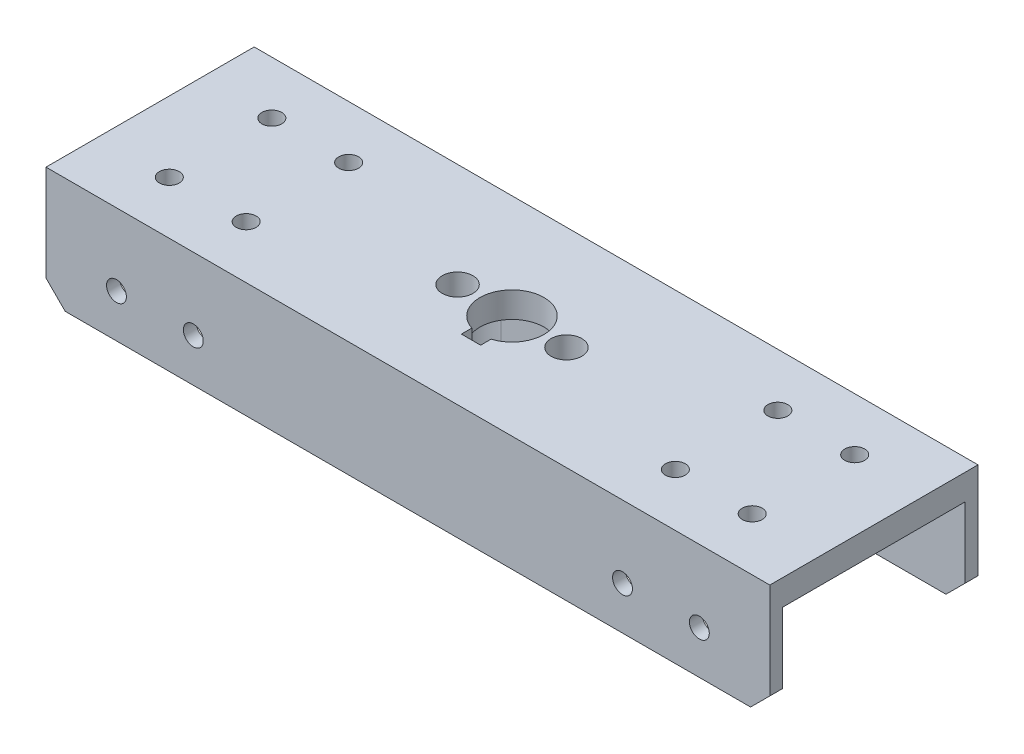
SolidWorks part; units mm, degrees
material "6061-T6 (SS)"
ref_plane "Front Plane" through (0, 0, 0) normal (0, 0, 1) x (1, 0, 0)
ref_plane "Top Plane" through (0, 0, 0) normal (0, 1, 0) x (1, 0, 0)
ref_plane "Right Plane" through (0, 0, 0) normal (1, 0, 0) x (0, 0, -1)
sketch "Sketch1" plane through (0, 0, 0) normal (0, 1, 0) x (1, 0, 0)
  line L1 (0, 0) -> (113, 0)
  line L2 (0, 0) -> (0, 32.5)
  line L3 (0, 32.5) -> (113, 32.5)
  line L4 (113, 0) -> (113, 32.5)
  dimension "D1" = 32.5
  dimension "D2" = 113
extrude "Boss-Extrude1" add sketch "Sketch1" along normal blind 4
sketch "Sketch4" plane through (0, 4, 0) normal (0, 1, 0) x (1, 0, 0)
  line L0 (56.5, 32.5) -> (56.5, -12.4802) construction
  line L1 (113, 32.5) -> (0, 32.5) construction
  line L3 (0, 16.25) -> (122.1673, 16.25) construction
  line L4 (0, 32.5) -> (0, 0) construction
  point P0 (11, 24.25)
  point P12 (23, 24.25)
  point P13 (23, 8.25)
  point P14 (11, 8.25)
  point P25 (102, 8.25)
  point P26 (90, 8.25)
  point P27 (90, 24.25)
  point P28 (102, 24.25)
  dimension "D1" = 2
  dimension "D3" = 12
  dimension "D4" = 16
  dimension "D5" = 8
  dimension "D6" = 79
  dimension "D2" = 2
hole_wizard "M2.5 Clearance Hole2" positions "Sketch4" profile "Sketch3" hole size "M2.5" standard "DIN" end condition through all
sketch "Sketch3" plane through (11, 4, -24.25) normal (1, 0, 0) x (0, 0, 1)
  line L0 (0, 0) -> (0, 4)
  line L1 (0, 4) -> (1.55, 4)
  line L2 (1.55, 4) -> (1.55, 0)
  line L5 (1.55, 0) -> (0, 0)
  line L11 (0, -6.35) -> (0, 107.95) construction
  dimension "Thru Hole Dia." = 3.1
  dimension "Thru Hole Depth" = 4
sketch "Sketch5" plane through (0, 0, 0) normal (0, -1, 0) x (1, 0, 0)
  line L0 (0, -16.25) -> (113, -16.25) construction
  line L1 (0, 0) -> (113, 0)
  line L3 (0, -32.5) -> (113, -32.5)
  line L5 (0, -2) -> (113, -2)
  line L7 (0, -30.5) -> (113, -30.5)
  line L9 (0, -16.25) -> (113, -16.25) construction
  line L20 (0, 0) -> (0, -2)
  line L23 (0, -32.5) -> (0, -30.5)
  line L24 (113, 0) -> (113, -2)
  line L25 (113, -30.5) -> (113, -32.5)
  dimension "D1" = 28.5
extrude "Boss-Extrude2" add sketch "Sketch5" along normal blind 14
sketch "Sketch7" plane through (0, -14, 0) normal (0, -1, 0) x (1, 0, 0)
  line L1 (0, -2) -> (113, -2) construction
  line L2 (34.5, -2) -> (78.5, -2)
  line L3 (34.5, -2) -> (34.5, -30.5)
  line L5 (113, -30.5) -> (0, -30.5) construction
  line L6 (34.5, -30.5) -> (78.5, -30.5)
  line L21 (78.5, -2) -> (78.5, -30.5)
  line L22 (113, -30.5) -> (0, -30.5) construction
  point P10 (56.5, -30.5)
  dimension "D1" = 44
extrude "Boss-Extrude3" add sketch "Sketch7" against normal up to next
sketch "Sketch10" plane through (0, 0, -32.5) normal (0, 0, -1) x (-1, 0, 0)
  line L1 (0, 0) -> (-34.5, 0) construction
  line L2 (-23, -7.25) -> (-11, -7.25)
  line L4 (-9.55, 1.1) -> (-12.45, 1.1)
  line L5 (-11, 1.1) -> (-11, -7.25)
  line L8 (-56.5, 4) -> (-56.5, -40.6573) construction
  line L9 (-113, 4) -> (0, 4) construction
  point P0 (-11, -7.25)
  point P2 (-23, -7.25)
  point P30 (-102, -7.25)
  point P31 (-90, -7.25)
  dimension "D1" = 7.25
  dimension "D2" = 12
hole_wizard "M2.5 Clearance Hole1" positions "Sketch10" profile "Sketch9" hole size "M2.5" standard "DIN" end condition through all
sketch "Sketch9" plane through (11, -7.25, -32.5) normal (1, 0, 0) x (0, 1, 0)
  line L0 (0, 0) -> (0, 32.5)
  line L1 (0, 32.5) -> (1.55, 32.5)
  line L2 (1.55, 32.5) -> (1.55, 0)
  line L5 (1.55, 0) -> (0, 0)
  line L11 (0, -6.35) -> (0, 107.95) construction
  dimension "Thru Hole Dia." = 3.1
  dimension "Thru Hole Depth" = 32.5
sketch "Sketch11" plane through (0, -14, 0) normal (0, -1, 0) x (1, 0, 0)
  line L24 (38.5, -4) -> (38.5, -28.5)
  line L25 (38.5, -28.5) -> (74.5, -28.5)
  line L26 (74.5, -28.5) -> (74.5, -4)
  line L27 (74.5, -4) -> (38.5, -4)
  line L28 (38.5, -4) -> (38.5, -28.5)
  line L29 (38.5, -28.5) -> (74.5, -28.5)
  line L30 (74.5, -28.5) -> (74.5, -4)
  line L31 (74.5, -4) -> (38.5, -4)
  dimension "D1" = 4
extrude "Cut-Extrude1" cut sketch "Sketch11" against normal blind 14
sketch "Sketch14" plane through (0, 4, 0) normal (0, 1, 0) x (1, 0, 0)
  line L0 (0, 32.5) -> (113, 0)
  line L1 (113, 0) -> (113, 32.5)
  line L2 (113, 32.5) -> (0, 0)
  point P12 (56.5, 16.25)
hole_wizard "Ø10.0mm Dowel Hole1" positions "Sketch14" profile "Sketch13" hole size "Ø10.0" standard "DIN" end condition through all
sketch "Sketch13" plane through (56.5, 4, -16.25) normal (1, 0, 0) x (0, 0, 1)
  line L0 (0, 0) -> (0, 18)
  line L1 (0, 18) -> (5, 18)
  line L2 (5, 18) -> (5, 0)
  line L5 (5, 0) -> (0, 0)
  line L11 (0, -6.35) -> (0, 107.95) construction
  dimension "Thru Hole Dia." = 10
  dimension "Thru Hole Depth" = 18
fillet "Fillet1" radius 4 4 edges at (38.5, -7, -28.5) (38.5, -7, -4) (74.5, -7, -4) (74.5, -7, -28.5)
sketch "Sketch15" plane through (0, -14, 0) normal (0, -1, 0) x (1, 0, 0)
  line L0 (0, -2) -> (34.5, -2) construction
  line L1 (34.5, -2) -> (34.5, -30.5) construction
  line L2 (78.5, -2) -> (78.5, -30.5) construction
  line L3 (34.5, -30.5) -> (0, -30.5) construction
  line L4 (78.5, -2) -> (113, -2) construction
  line L5 (113, -30.5) -> (78.5, -30.5) construction
  circle A0 centre (34.5, -4.75) radius 2.75
  circle A1 centre (34.5, -27.75) radius 2.75
  circle A2 centre (78.5, -4.75) radius 2.75
  circle A3 centre (78.5, -27.75) radius 2.75
  dimension "D1" = 5.5
extrude "Cut-Extrude2" cut sketch "Sketch15" against normal up to surface (14 mm away) and the other way through all up to face at (17.25, 0, -16.25)
fillet "Fillet2" radius 3 4 edges at (78.5, -7, -25) (78.5, -7, -7.5) (34.5, -7, -25) (34.5, -7, -7.5)
chamfer "Chamfer1" distance 3 angle 45 4 edges at (113, -14, -31.5) (113, -14, -1) (0, -14, -31.5) (0, -14, -1)
sketch "Sketch20" plane through (0, 0, 0) normal (0, -1, 0) x (1, 0, 0)
  line L1 (55, -11.4803) -> (58, -11.4803)
  line L2 (55, -11.4803) -> (55, -9.85)
  line L3 (55, -9.85) -> (58, -9.85)
  line L4 (58, -11.4803) -> (58, -9.85)
  circle A0 centre (56.5, -16.25) radius 5 construction
  point P6 (56.5, -11.25)
  dimension "D1" = 1.4
  dimension "D2" = 3
extrude "Cut-Extrude4" cut sketch "Sketch20" against normal through all
sketch "Sketch23" plane through (0, 0, 0) normal (0, -1, 0) x (-1, 0, 0)
  circle A0 centre (-56.5, 16.25) radius 8.5
  point P4 (-65, 16.25)
  point P6 (-48, 16.25)
  dimension "D1" = 17
hole_wizard "M4 Clearance Hole2" positions "Sketch23" profile "Sketch22" hole size "M4" standard "DIN" end condition through all
sketch "Sketch22" plane through (48, 0, -16.25) normal (1, 0, 0) x (0, 0, -1)
  line L0 (0, 0) -> (0, 4)
  line L1 (0, 4) -> (2.4, 4)
  line L2 (2.4, 4) -> (2.4, 0)
  line L5 (2.4, 0) -> (0, 0)
  line L11 (0, -6.35) -> (0, 107.95) construction
  dimension "Thru Hole Dia." = 4.8
  dimension "Thru Hole Depth" = 4
